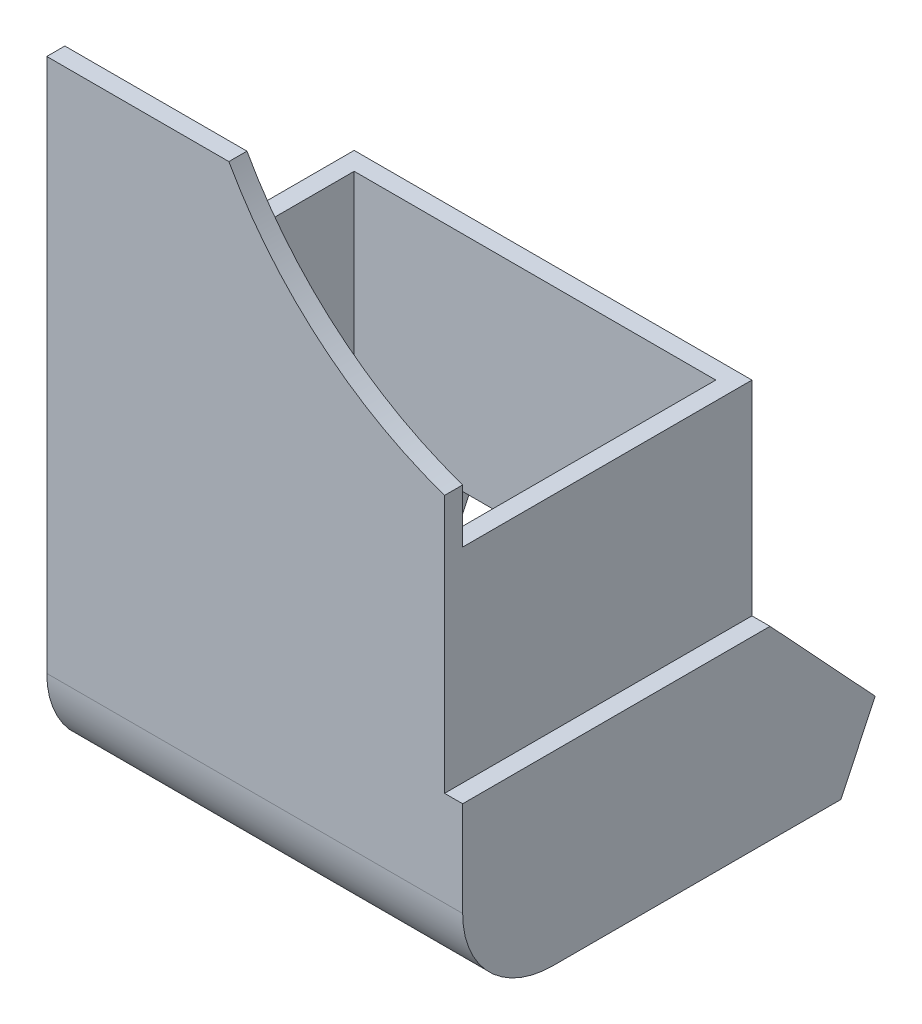
SolidWorks part; units mm, degrees
ref_plane "Front Plane" through (0, 0, 0) normal (0, 0, 1) x (1, 0, 0)
ref_plane "Top Plane" through (0, 0, 0) normal (0, 1, 0) x (1, 0, 0)
ref_plane "Right Plane" through (0, 0, 0) normal (1, 0, 0) x (0, 0, -1)
sketch "Sketch1" plane through (0, 0, 0) normal (0, 1, 0) x (1, 0, 0)
  line L1 (0, 0) -> (23, 0)
  line L2 (0, 0) -> (0, 17)
  line L3 (0, 17) -> (23, 17)
  line L4 (23, 0) -> (23, 17)
  dimension "D1" = 23
  dimension "D2" = 17
extrude "Boss-Extrude1" add sketch "Sketch1" along normal blind 10.256
sketch "Sketch2" plane through (23, 0, 0) normal (1, 0, 0) x (0, 0, -1)
  line L0 (17, 0) -> (20.918, 0)
  line L1 (20.918, 0) -> (22.8166, 4.0003)
  line L2 (22.8166, 4.0003) -> (17, 10.256)
  line L3 (17, 10.256) -> (17, 0)
  dimension "D1" = 3.918
  dimension "D2" = 4.428
  dimension "D3" = 115.39
extrude "Boss-Extrude2" add sketch "Sketch2" against normal blind 23
shell "Shell1" thickness 1.044 removed face at (11.5, 2.0002, -21.8673)
sketch "Sketch3" plane through (0, 10.256, 0) normal (0, 1, 0) x (1, 0, 0)
  line L0 (23, 17) -> (0, 17) construction
  line L1 (0, 0) -> (22, 0)
  line L2 (0, 0) -> (0, 17)
  line L3 (0, 17) -> (22, 17)
  line L4 (22, 0) -> (22, 17)
  line L5 (23, 0) -> (23, 17) construction
  dimension "D1" = 1
extrude "Boss-Extrude3" add sketch "Sketch3" along normal blind 24.294
shell "Shell2" thickness 1 removed face at (11, 34.55, -8.5)
sketch "Sketch4" plane through (0, 10.212, 0) normal (0, 1, 0) x (1, 0, 0)
  line L4 (21, 1) -> (21, 16)
  line L5 (21, 16) -> (1, 16)
  line L6 (1, 16) -> (1, 1)
  line L7 (1, 1) -> (21, 1)
  line L8 (21, 1) -> (21, 16)
  line L9 (21, 16) -> (1, 16)
  line L10 (1, 16) -> (1, 1)
  line L11 (1, 1) -> (21, 1)
  dimension "D1" = 0
extrude "Cut-Extrude1" cut sketch "Sketch4" against normal blind 3.294
sketch "Sketch5" plane through (22, 0, 0) normal (1, 0, 0) x (0, 0, -1)
  line L2 (0, 34.55) -> (17, 34.55) construction
  line L3 (1, 34.55) -> (17, 34.55)
  line L4 (1, 34.55) -> (1, 21.55)
  line L5 (1, 21.55) -> (17, 21.55)
  line L6 (17, 34.55) -> (17, 21.55)
  line L7 (0, 34.55) -> (0, 10.256) construction
  line L8 (17, 34.55) -> (17, 10.256) construction
  dimension "D1" = 1
  dimension "D2" = 13
extrude "Cut-Extrude2" cut sketch "Sketch5" against normal blind 26.294
sketch "Sketch6" plane through (0, 0, 0) normal (0, 0, 1) x (1, 0, 0)
  line L0 (22, 34.55) -> (10.0701, 34.55)
  line L1 (22, 34.55) -> (22, 10.256) construction
  line L2 (0, 34.55) -> (22, 34.55) construction
  line L3 (22, 34.55) -> (22, 24.5273)
  arc A0 (10.0701, 34.55) -> (22, 24.5273) centre (29.1849, 45.1907) ccw
  dimension "D1" = 21.8769
  dimension "D2" = 11.9299
  dimension "D3" = 10.0227
extrude "Cut-Extrude3" cut sketch "Sketch6" against normal blind 26.294
fillet "Fillet1" radius 5 1 edges at (11.5, 0, 0)
fillet "Fillet2" radius 5 1 edges at (11.5, 1.044, -1.044)
